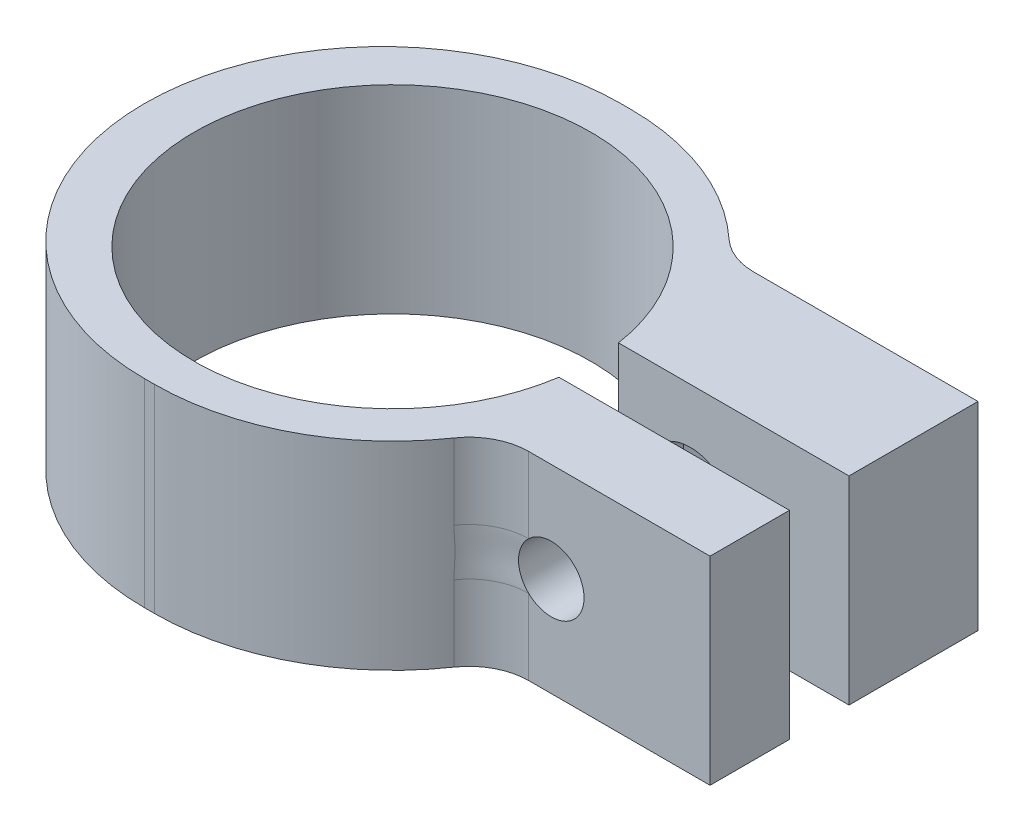
SolidWorks part; units mm, degrees
ref_plane "前视基准面" through (0, 0, 0) normal (0, 0, 1) x (1, 0, 0)
ref_plane "上视基准面" through (0, 0, 0) normal (0, 1, 0) x (1, 0, 0)
ref_plane "右视基准面" through (0, 0, 0) normal (1, 0, 0) x (0, 0, -1)
sketch "草图1" plane through (0, 0, 0) normal (0, 1, 0) x (1, 0, 0)
  line L1 (-17, -12) -> (17, -12)
  line L2 (-17, -12) -> (-17, 12)
  line L3 (-17, 12) -> (17, 12)
  line L4 (17, -12) -> (17, 12)
  line L5 (-17, -12) -> (17, 12) construction
  line L6 (-17, 12) -> (17, -12) construction
  point P0 (0, 0)
  dimension "D1" = 34
  dimension "D2" = 24
extrude "凸台-拉伸1" add sketch "草图1" along normal blind 10
sketch "草图3" plane through (0, 10, 0) normal (0, 1, 0) x (1, 0, 0)
  line L0 (0, 0) -> (-14.5, 0) construction
  line L1 (-17, 12) -> (-17, -12) construction
  circle A0 centre (-4.5, 0) radius 10
  dimension "D1" = 2.5
  dimension "D2" = 20
extrude "切除-拉伸2" cut sketch "草图3" against normal through all
sketch "草图6" plane through (0, 0, -12) normal (0, 0, -1) x (-1, 0, 0)
  line L0 (-17, 5) -> (-1, 5) construction
  line L1 (-17, 10) -> (-17, 0) construction
  dimension "D1" = 16
sketch "草图13" plane through (0, 0, 0) normal (0, -1, 0) x (1, 0, 0)
  line L0 (6.1654, 5.5) -> (21.7344, 5.5)
  line L1 (21.7344, 5.5) -> (21.7344, 14.3404)
  line L2 (21.7344, 14.3404) -> (-4.5, 14.3404)
  line L3 (-4.5, 14.3404) -> (-4.5, 12)
  line L4 (4.4443, -8) -> (17, -8)
  line L5 (17, -8) -> (17, -12)
  line L6 (17, -12) -> (-4.5, -12)
  line L7 (-17, 12) -> (17, 12) construction
  line L8 (17, -12) -> (-17, -12) construction
  arc A0 (-4.5, -12) -> (4.4443, -8) centre (-4.5, 0) ccw
  arc A1 (6.1654, 5.5) -> (-4.5, 12) centre (-4.5, 0) ccw
  dimension "D1" = 24
  dimension "D2" = 4
  dimension "D3" = 6.5
extrude "切除-拉伸4" cut sketch "草图13" against normal through all
hole_wizard "打孔尺寸(%根据)内六角圆柱头螺钉的类型1" positions "草图7" profile "草图8" counterbore size "M4" standard "GB"
sketch "草图7" plane through (0, 0, -8) normal (0, 0, -1) x (-1, 0, 0)
  line L0 (-17, 5) -> (-1, 5) construction
  point P0 (-9, 5)
sketch "草图8" plane through (9, 5, -8) normal (1, 0, 0) x (0, 1, 0)
  line L0 (0, 0) -> (0, 9.3519)
  line L1 (0, 9.3519) -> (2.25, 8)
  line L2 (2.25, 8) -> (2.25, 4.6)
  line L3 (2.25, 4.6) -> (4, 4.6)
  line L4 (4, 4.6) -> (4, 0)
  line L5 (4, 0) -> (0, 0)
  line L10 (0, 9.3519) -> (-2.25, 8) construction
  line L11 (0, -6.35) -> (0, 107.95) construction
  dimension "孔直径" = 4.5
  dimension "孔深度" = 8
  dimension "柱形沉头孔直径" = 8
  dimension "柱形沉头孔深度" = 4.6
  dimension "导头角度" = 118
sketch "草图4" plane through (0, 10, 0) normal (0, 1, 0) x (1, 0, 0)
  line L0 (0, 0) -> (32.7572, 0)
extrude "切除-拉伸-薄壁1" cut sketch "草图4" against normal through all and the other way through all thin thin type mid plane wall 3
hole_wizard "M4 螺纹孔1" positions "草图9" profile "草图11" tap size "M4" standard "GB" end condition through all
sketch "草图9" plane through (0, 0, 1.5) normal (0, 0, -1) x (-1, 0, 0)
  line L0 (-17, 5) -> (-1, 5) construction
  point P0 (-9, 5)
sketch "草图11" plane through (9, 5, 1.5) normal (1, 0, 0) x (0, 1, 0)
  line L0 (0, 0) -> (0, 10.5)
  line L1 (0, 10.5) -> (1.65, 10.5)
  line L2 (1.65, 10.5) -> (1.65, 0)
  line L5 (1.65, 0) -> (0, 0)
  line L11 (0, -6.35) -> (0, 107.95) construction
  dimension "通孔螺纹孔钻头直径" = 3.3
  dimension "通孔螺纹孔钻头深度" = 10.5
cosmetic thread "孔螺蚊线1" parameters "D2"=4
fillet "圆角2" radius 12 2 edges at (-17, 5, 12) (-17, 5, -12)
fillet "圆角3" radius 3 2 edges at (6.1654, 5, 5.5) (4.4443, 5, -8)
